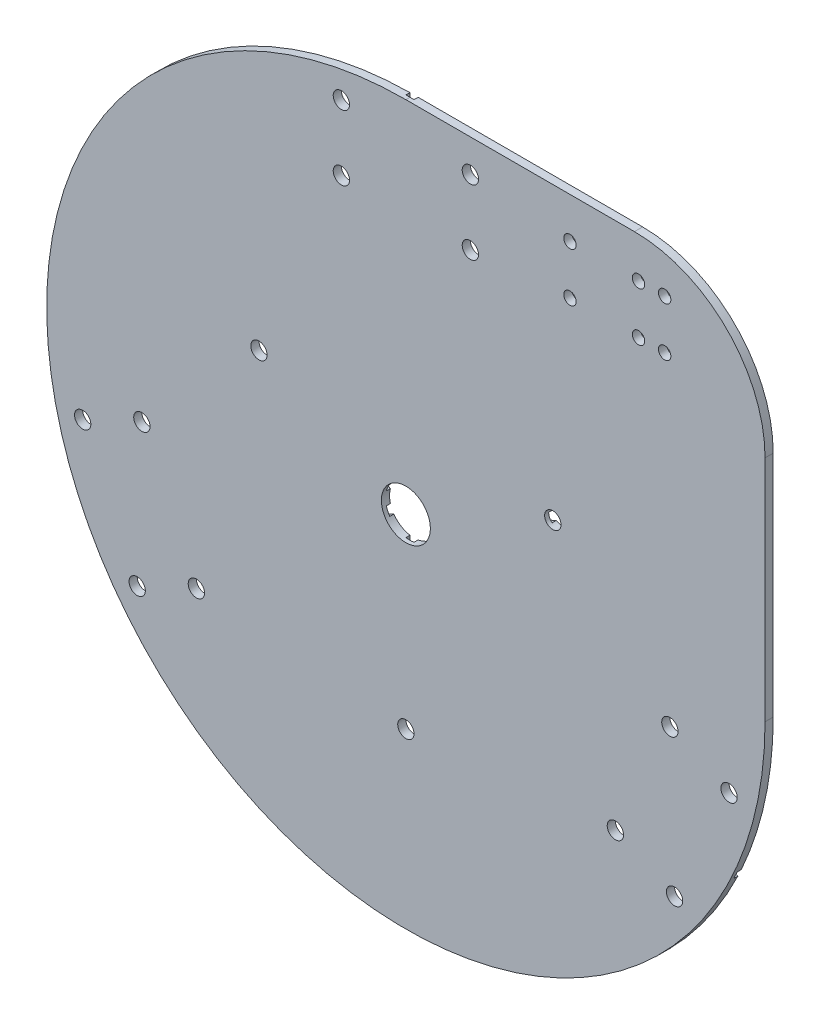
SolidWorks part; units mm, degrees
ref_plane "Front Plane" through (0, 0, 0) normal (0, 0, 1) x (1, 0, 0)
ref_plane "Top Plane" through (0, 0, 0) normal (0, 1, 0) x (1, 0, 0)
ref_plane "Right Plane" through (0, 0, 0) normal (1, 0, 0) x (0, 0, -1)
sketch "Sketch1" plane through (0, 0, 0) normal (0, 0, 1) x (1, 0, 0)
  line L0 (0, 139.7) -> (139.7, 139.7)
  line L1 (139.7, 139.7) -> (139.7, 0)
  arc A0 (0, 139.7) -> (139.7, 0) centre (0, 0) ccw
  dimension "D1" = 279.4
extrude "Boss-Extrude1" add sketch "Sketch1" along normal blind 3.175
sketch "Sketch2" plane through (0, 0, 0) normal (0, 0, -1) x (-1, 0, 0)
  line L0 (0, -139.7) -> (0, 139.7) construction
  line L1 (-139.7, 0) -> (139.7, 0) construction
  line L2 (-126.6112, -59.0398) -> (-126.6112, 0) construction
  line L3 (126.6112, -59.0398) -> (126.6112, 0) construction
  line L4 (-57.15, 26.6495) -> (0, -72.3372) construction
  line L5 (-126.6112, -59.0398) -> (126.6112, 59.0398) construction
  line L6 (126.6112, -59.0398) -> (-126.6112, 59.0398) construction
  line L7 (-125.9403, -60.4785) -> (127.2821, 57.601)
  line L8 (127.2821, -57.601) -> (-125.9403, 60.4785)
  line L9 (1.5875, -139.7) -> (1.5875, 139.7)
  line L10 (-127.2821, -57.601) -> (125.9403, 60.4785)
  line L11 (125.9403, -60.4785) -> (-127.2821, 57.601)
  line L12 (-1.5875, -139.7) -> (-1.5875, 139.7)
  line L13 (0, -72.3372) -> (57.15, 26.6495) construction
  line L14 (57.15, 26.6495) -> (-57.15, 26.6495) construction
  line L15 (0, 139.7) -> (-139.7, 139.7)
  line L16 (0, 139.7) -> (-139.7, 139.7)
  line L17 (-139.7, 139.7) -> (-139.7, 0)
  line L18 (-139.7, 139.7) -> (-139.7, 0)
  circle A0 centre (0, 0) radius 139.7 construction
  arc A2 (-139.7, 0) -> (0, 139.7) centre (0, 0) ccw
  arc A3 (-139.7, 0) -> (0, 139.7) centre (0, 0) ccw
  circle A4 centre (-57.15, 26.6495) radius 3.175
  circle A5 centre (57.15, 26.6495) radius 3.175
  circle A6 centre (0, -72.3372) radius 3.175
  point P6 (0, 0)
  point P11 (0, 0)
  arc M9 (-139.7, 0) -> (0, 139.7) centre (0, 0) ccw
  dimension "D5" = 6.35
  dimension "D1" = 25
  dimension "D6" = 114.3
  dimension "D2" = 1.5875
  dimension "D3" = 1.5875
  dimension "D4" = 0
extrude "Cut-Extrude3" cut sketch "Sketch2" against normal blind 1.5875 contours L7 L12 L11 L10 M9 | L12 L7 L11 | L12 L11 L7 L9 L8 L10 | L11 L9 L7 | L11 L12 L10 | L12 L10 L8 | L10 L8 L9 | L9 L7 L8 | L10 L9 L8 L7 M9 | L11 L8 L7 L9 M9 | L12 L8 L10 L9 M9 | L10 L12 L8 L11 M9 | L12 L9 L11 L7 M9 region at (64.4096, -30.037, 0) region at (1.0583, -1.7516, 0) region at (0, -35.7106, 0) region at (0, 0, 0) region at (-1.0583, -1.7516, 0) region at (2.3104, 0, 0) region at (28.3021, 13.2029, 0) region at (-2.3104, 0, 0) region at (-64.4096, -30.037, 0) region at (1.0583, 1.7516, 0) region at (-28.3021, 13.2029, 0) region at (-1.0583, 1.7516, 0) region at (0, 70.91, 0)
sketch "Sketch3" plane through (0, 0, 3.175) normal (0, 0, 1) x (1, 0, 0)
  circle A0 centre (0, 0) radius 9.525
  dimension "D1" = 19.05
extrude "Cut-Extrude4" cut sketch "Sketch3" against normal through all
extrude "Cut-Extrude5" cut sketch "Sketch2<4>" against normal through all contours L8 A4 L11 | L11 A4 | L8 A4 | L7 A5 L10 | L10 A5 | L7 A5 | L12 A6 | L9 A6 L12 | L9 A6 region at (0, -72.3372, 0) region at (2.2384, -72.3372, 0) region at (-2.2384, -72.3372, 0) region at (58.096, 24.6208, 0) region at (57.15, 26.6495, 0) region at (-57.15, 26.6495, 0) region at (-58.096, 24.6208, 0) region at (56.204, 28.6782, 0) region at (-56.204, 28.6782, 0)
sketch "Sketch2<4>" plane through (0, 0, 0) normal (0, 0, -1) x (-1, 0, 0) same geometry as "Sketch2"
fillet "Fillet1" radius 50.8 1 edges at (139.7, 139.7, 1.5875)
sketch "Sketch4" plane through (0, 0, 3.175) normal (0, 0, 1) x (1, 0, 0)
  line L0 (35.921, 139.7) -> (35.921, 88.9)
  line L1 (35.921, 88.9) -> (139.7, 88.9)
  line L2 (139.7, 0) -> (139.7, 88.9)
  line L3 (88.9, 139.7) -> (0, 139.7)
  line L4 (139.7, 0) -> (139.7, 88.9)
  line L5 (88.9, 139.7) -> (0, 139.7)
  arc A2 (139.7, 88.9) -> (88.9, 139.7) centre (88.9, 88.9) ccw
  arc A3 (0, 139.7) -> (139.7, 0) centre (0, 0) ccw
  arc A4 (139.7, 88.9) -> (88.9, 139.7) centre (88.9, 88.9) ccw
  arc A5 (0, 139.7) -> (139.7, 0) centre (0, 0) ccw
  point P8 (124.821, 124.821)
  dimension "D2" = 88.9
  dimension "D3" = 50.8
  dimension "D1" = 0
sketch "Sketch8" plane through (0, 0, 3.175) normal (0, 0, 1) x (1, 0, 0)
  circle A0 centre (25.0825, 101.6) radius 3.175 construction
  circle A1 centre (-25.0825, 101.6) radius 3.175 construction
  circle A2 centre (-25.0825, 127) radius 3.175 construction
  circle A3 centre (25.0825, 127) radius 3.175 construction
  circle A4 centre (102.6812, -20.2056) radius 3.175 construction
  circle A5 centre (125.7014, -30.9401) radius 3.175 construction
  circle A6 centre (81.4805, -65.6705) radius 3.175 construction
  circle A7 centre (104.5008, -76.405) radius 3.175 construction
  circle A8 centre (-81.4805, -65.6705) radius 3.175 construction
  circle A9 centre (-104.5008, -76.405) radius 3.175 construction
  circle A10 centre (-102.6812, -20.2056) radius 3.175 construction
  circle A11 centre (-125.7014, -30.9401) radius 3.175 construction
  circle A12 centre (25.0825, 101.6) radius 3.175
  circle A13 centre (-25.0825, 101.6) radius 3.175
  circle A14 centre (-25.0825, 127) radius 3.175
  circle A15 centre (25.0825, 127) radius 3.175
  circle A16 centre (102.6812, -20.2056) radius 3.175
  circle A17 centre (125.7014, -30.9401) radius 3.175
  circle A18 centre (81.4805, -65.6705) radius 3.175
  circle A19 centre (104.5008, -76.405) radius 3.175
  circle A20 centre (-81.4805, -65.6705) radius 3.175
  circle A21 centre (-104.5008, -76.405) radius 3.175
  circle A22 centre (-102.6812, -20.2056) radius 3.175
  circle A23 centre (-125.7014, -30.9401) radius 3.175
extrude "Cut-Extrude7" cut sketch "Sketch8" against normal through all
sketch "Sketch9" plane through (0, 0, 3.175) normal (0, 0, 1) x (1, 0, 0)
  circle A0 centre (90.4875, 104.775) radius 2.413 construction
  circle A1 centre (90.4875, 123.825) radius 2.413 construction
  circle A2 centre (100.6475, 104.775) radius 2.413 construction
  circle A3 centre (100.6475, 123.825) radius 2.413 construction
  circle A4 centre (63.8175, 104.775) radius 2.413 construction
  circle A5 centre (63.8175, 123.825) radius 2.413 construction
  circle A6 centre (90.4875, 104.775) radius 2.413
  circle A7 centre (90.4875, 123.825) radius 2.413
  circle A8 centre (100.6475, 104.775) radius 2.413
  circle A9 centre (100.6475, 123.825) radius 2.413
  circle A10 centre (63.8175, 104.775) radius 2.413
  circle A11 centre (63.8175, 123.825) radius 2.413
extrude "Cut-Extrude8" cut sketch "Sketch9" against normal through all
